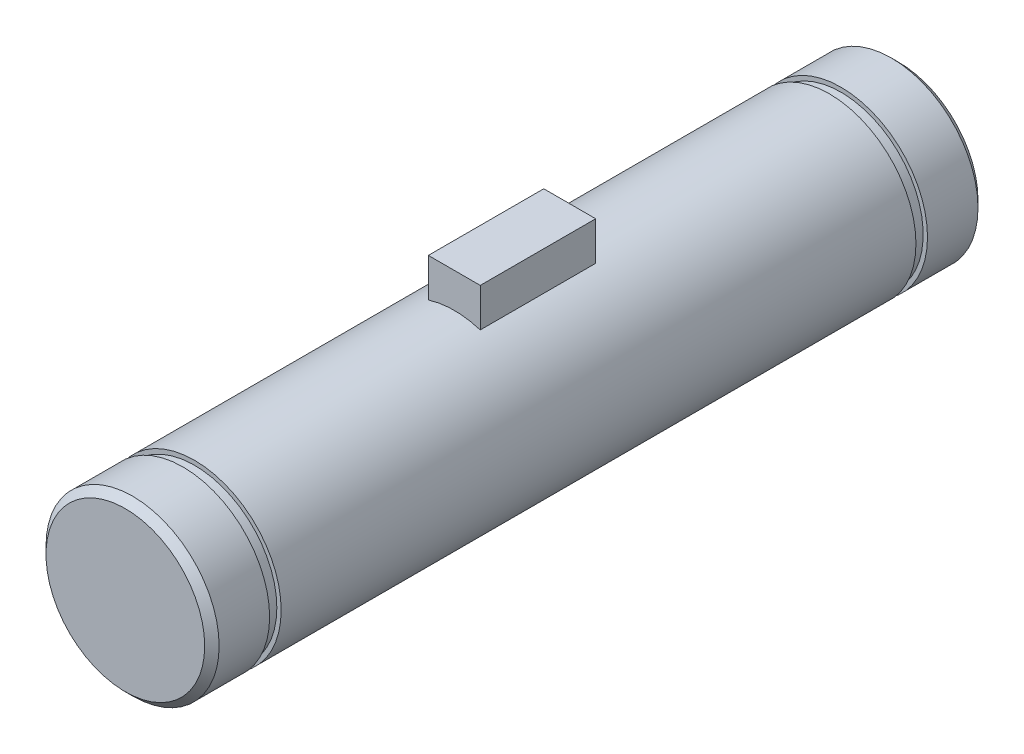
SolidWorks part; units mm, degrees
ref_plane "Спереди" through (0, 0, 0) normal (0, 0, 1) x (1, 0, 0)
ref_plane "Сверху" through (0, 0, 0) normal (0, 1, 0) x (1, 0, 0)
ref_plane "Справа" through (0, 0, 0) normal (1, 0, 0) x (0, 0, -1)
sketch "Sketch1" plane through (0, 0, 0) normal (0, 0, 1) x (1, 0, 0)
  circle A0 centre (0, 0) radius 3
  dimension "D1" = 6
extrude "Boss-Extrude1" add sketch "Sketch1" along normal blind 26.8
sketch "Sketch2" plane through (0, 0, 0) normal (0, 0, -1) x (-1, 0, 0)
  line L0 (0.9, 0) -> (0.9, 4.2)
  line L1 (0.9, 4.2) -> (-0.9, 4.2)
  line L2 (-0.9, 4.2) -> (-0.9, 0)
  line L3 (-0.9, 0) -> (0.9, 0)
  dimension "D1" = 1.8
  dimension "D2" = 4.2
  dimension "D3" = 0.9
  dimension "D4" = 0
extrude "Boss-Extrude2" add sketch "Sketch2" against normal blind 4 from offset 11.4 offset against normal yes
sketch "Sketch3" plane through (0, 0, 0) normal (0, 0, -1) x (-1, 0, 0)
  circle A0 centre (0, 0) radius 2.85
  circle A1 centre (0, 0) radius 3
  dimension "D1" = 5.7
extrude "Cut-Extrude1" cut sketch "Sketch3" against normal blind 0.4 from offset 2 offset against normal yes
sketch "Sketch4" plane through (0, 0, 26.8) normal (0, 0, 1) x (1, 0, 0)
  circle A0 centre (0, 0) radius 2.85
  circle A1 centre (0, 0) radius 3.001
  dimension "D1" = 5.7
extrude "Cut-Extrude2" cut sketch "Sketch4" against normal blind 0.4 from offset 2 offset against normal yes
chamfer "Chamfer1" distance 0.25 angle 45 2 edges at (3, 0, 0) (3, 0, 26.8)
